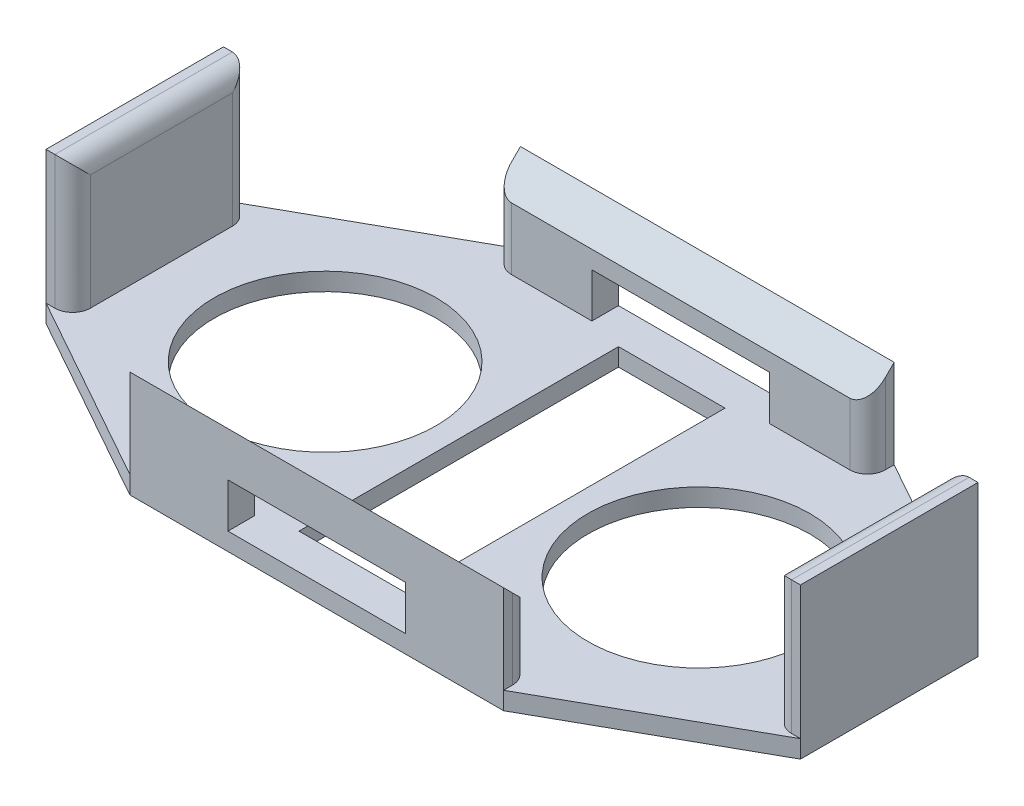
SolidWorks part; units mm, degrees
ref_plane "Front Plane" through (0, 0, 0) normal (0, 0, 1) x (1, 0, 0)
ref_plane "Top Plane" through (0, 0, 0) normal (0, 1, 0) x (1, 0, 0)
ref_plane "Right Plane" through (0, 0, 0) normal (1, 0, 0) x (0, 0, -1)
ref_plane "Plane1" through (0, 5, 0) normal (0, 1, 0) x (1, 0, 0)
sketch "Sketch1" plane through (0, 5, 0) normal (0, 1, 0) x (1, 0, 0)
  line L1 (0, 0) -> (85, 0)
  line L2 (0, 0) -> (0, 44)
  line L3 (0, 44) -> (85, 44)
  line L4 (85, 0) -> (85, 44)
  dimension "D1" = 85
  dimension "D2" = 44
extrude "Boss-Extrude1" add sketch "Sketch1" along normal blind 2
sketch "Sketch2" plane through (0, 7, 0) normal (0, 1, 0) x (1, 0, 0)
  line L0 (0, 22) -> (85, 22) construction
  line L1 (0, 44) -> (0, 0) construction
  line L2 (85, 0) -> (85, 44) construction
  line L3 (42.5, 44) -> (42.5, 0) construction
  line L4 (0, 12) -> (3, 12)
  line L5 (0, 12) -> (0, 32)
  line L6 (0, 32) -> (3, 32)
  line L7 (3, 12) -> (3, 32)
  line L8 (85, 44) -> (0, 44) construction
  line L9 (0, 0) -> (85, 0) construction
  line L10 (85, 32) -> (82, 32)
  line L11 (82, 12) -> (82, 32)
  line L12 (85, 12) -> (82, 12)
  line L13 (85, 12) -> (85, 32)
  point P10 (0, 22)
  dimension "D1" = 3
  dimension "D2" = 20
extrude "Boss-Extrude2" add sketch "Sketch2" along normal blind 15
sketch "Sketch3" plane through (0, 7, 0) normal (0, 1, 0) x (1, 0, 0)
  line L0 (42.5, 44) -> (42.5, 0) construction
  line L1 (85, 44) -> (0, 44) construction
  line L2 (0, 0) -> (85, 0) construction
  line L3 (0, 22) -> (85, 22) construction
  line L4 (0, 32) -> (0, 12) construction
  line L5 (85, 12) -> (85, 32) construction
  line L6 (21.4483, 44) -> (63.5517, 44)
  line L7 (21.4483, 3) -> (63.5517, 3)
  line L8 (21.4483, 3) -> (21.4483, 0)
  line L9 (21.4483, 0) -> (63.5517, 0)
  line L10 (63.5517, 3) -> (63.5517, 0)
  line L15 (63.5517, 41) -> (63.5517, 44)
  line L16 (21.4483, 41) -> (63.5517, 41)
  line L17 (21.4483, 41) -> (21.4483, 44)
  point P16 (42.5, 0)
  dimension "D1" = 3
extrude "Boss-Extrude3" add sketch "Sketch3" along normal blind 10
sketch "Sketch4" plane through (0, 0, 0) normal (0, 0, 1) x (1, 0, 0)
  line L0 (14.0808, 7) -> (72.6916, 7) construction
  line L3 (0, 7) -> (21.4483, 7) construction
  line L4 (42.5, 17) -> (42.5, 5) construction
  line L5 (21.4483, 17) -> (63.5517, 17) construction
  line L6 (24.2, 5) -> (-24.2, 5) construction
  line L8 (32.5, 12) -> (52.5, 12)
  line L9 (32.5, 12) -> (32.5, 7)
  line L10 (32.5, 7) -> (52.5, 7)
  line L11 (52.5, 12) -> (52.5, 7)
  point P14 (42.5, 7)
  dimension "D1" = 5
  dimension "D2" = 20
extrude "Cut-Extrude1" cut sketch "Sketch4" against normal through all
chamfer "Chamfer1" distance 3 angle 45 2 edges at (42.5, 17, -3) (42.5, 17, -41)
sketch "Sketch6" plane through (0, 5, 0) normal (0, 1, 0) x (1, 0, 0)
  line L0 (0, 32) -> (21.4483, 44)
  line L1 (21.4483, 44) -> (63.5517, 44)
  line L2 (63.5517, 44) -> (85, 32)
  line L3 (85, 32) -> (85, 12)
  line L4 (85, 12) -> (63.5517, 0)
  line L5 (63.5517, 0) -> (21.4483, 0)
  line L6 (21.4483, 0) -> (0, 12)
  line L8 (0, 32) -> (0, 12)
  line L9 (0, 22) -> (85, 22) construction
  line L10 (42.5, 44) -> (42.5, 0) construction
  line L13 (36.5, 4) -> (48.5, 4)
  line L14 (36.5, 4) -> (36.5, 40)
  line L15 (48.5, 4) -> (48.5, 40)
  line L16 (36.5, 40) -> (48.5, 40)
  line L17 (36.5, 4) -> (48.5, 40) construction
  line L18 (48.5, 4) -> (36.5, 40) construction
  circle A0 centre (21.4483, 22) radius 12.5
  circle A1 centre (63.5517, 22) radius 12.5
  point P20 (21.4483, 22)
  point P21 (63.5517, 22)
  point P29 (42.5, 22)
  dimension "D1" = 25
  dimension "D2" = 25
  dimension "D3" = 12
  dimension "D4" = 36
fillet "Fillet1" radius 2 14 edges at (85, 6, -44) (0, 6, -44) (0, 6, 0) (85, 6, 0) (82, 22, -22) (3, 22, -22) (3, 14.5, -32) (3, 14.5, -12) (21.4483, 10.5, -3) (63.5517, 10.5, -3) (63.5517, 10.5, -41) (21.4483, 10.5, -41) (82, 14.5, -12) (82, 14.5, -32)
extrude "Cut-Extrude3" cut sketch "Sketch6" along normal up to surface (2 mm away) flip side to cut up to face at (42.5, 7, -22)
